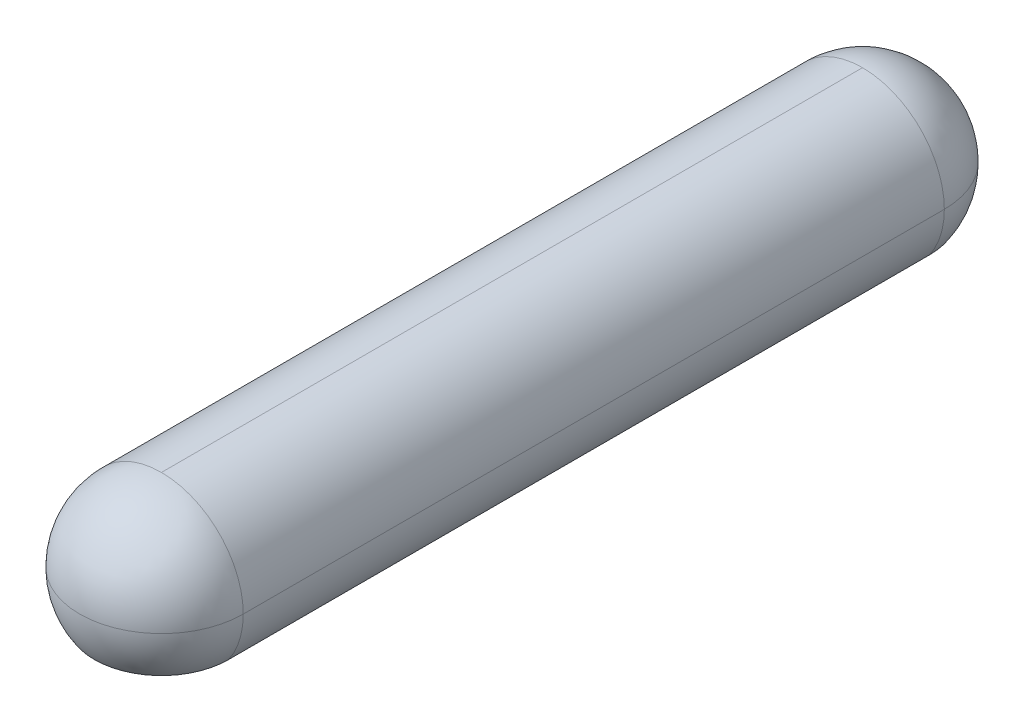
SolidWorks part; units mm, degrees
ref_plane "Front Plane" through (0, 0, 0) normal (0, 0, 1) x (1, 0, 0)
ref_plane "Top Plane" through (0, 0, 0) normal (0, 1, 0) x (1, 0, 0)
ref_plane "Right Plane" through (0, 0, 0) normal (1, 0, 0) x (0, 0, -1)
sketch "Sketch1" plane through (0, 0, 0) normal (0, 1, 0) x (1, 0, 0)
  line L0 (-7, 0) -> (-7, 60)
  line L2 (7, 60) -> (7, 0)
  arc A0 (-7, 0) -> (7, 0) centre (0, 0) ccw
  arc A1 (-7, 60) -> (7, 60) centre (0, 60) cw
  dimension "D1" = 7
  dimension "D2" = 60
extrude "Boss-Extrude1" add sketch "Sketch1" along normal blind 14
fillet "Fillet2" radius 7 4 edges at (-7, 14, -30) (0, 14, 7) (7, 14, -30) (0, 14, -67)
fillet "Fillet3" radius 7 4 edges at (-7, 0, -30) (0, 0, 7) (7, 0, -30) (0, 0, -67)
sketch "Sketch2" plane through (0, 0, 0) normal (0, 0, -1) x (-1, 0, 0)
  line L1 (-5.7446, 0) -> (5.7446, 0)
  line L2 (-5.7446, 0) -> (-5.7446, 3)
  line L3 (-5.7446, 3) -> (5.7446, 3)
  line L4 (5.7446, 0) -> (5.7446, 3)
  arc A2 (-7, 7) -> (0, 0) centre (0, 7) ccw construction
  arc A3 (0, 0) -> (7, 7) centre (0, 7) ccw construction
  dimension "D1" = 3
extrude "Cut-Extrude1" cut sketch "Sketch2" against normal through all and the other way through all
sketch "Sketch3" plane through (0, 3, 0) normal (0, -1, 0) x (1, 0, 0)
  line L0 (-3.75, 0) -> (-2.2411, -16.9329)
  line L2 (2.2411, -16.9329) -> (3.75, 0)
  arc A0 (3.75, 0) -> (-3.75, 0) centre (0, 0) ccw
  arc A1 (-2.2411, -16.9329) -> (2.2411, -16.9329) centre (0, -16.7332) ccw
  dimension "D1" = 3.75
  dimension "D2" = 2.25
  dimension "D3" = 17
  dimension "D4" = 17
extrude "Cut-Extrude2" cut sketch "Sketch3" against normal blind 4
